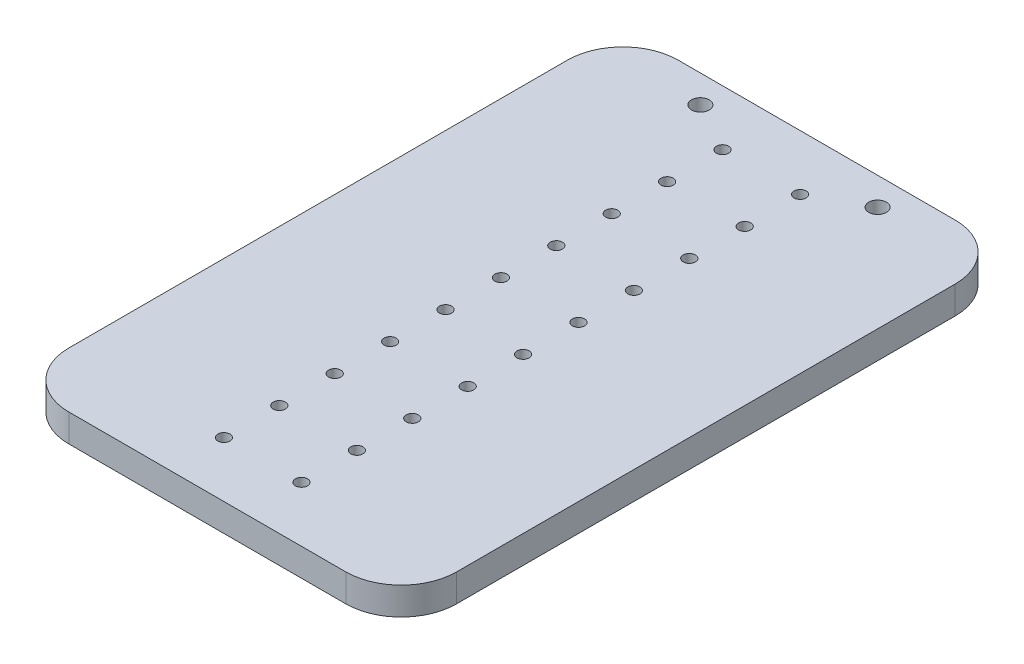
SolidWorks part; units mm, degrees
ref_plane "前视基准面" through (0, 0, 0) normal (0, 0, 1) x (1, 0, 0)
ref_plane "上视基准面" through (0, 0, 0) normal (0, 1, 0) x (1, 0, 0)
ref_plane "右视基准面" through (0, 0, 0) normal (1, 0, 0) x (0, 0, -1)
sketch "草图1" plane through (0, 0, 0) normal (0, 1, 0) x (1, 0, 0)
  line L0 (0, -113.2634) -> (0, 113.2634) construction
  line L1 (-35, 55) -> (35, 55)
  line L2 (-35, 55) -> (-35, -55)
  line L3 (-35, -55) -> (35, -55)
  line L4 (35, 55) -> (35, -55)
  line L5 (-35, 55) -> (35, -55) construction
  line L6 (-35, -55) -> (35, 55) construction
  circle A0 centre (-16, 50) radius 1.6
  circle A1 centre (-7, 35) radius 1.1
  circle A2 centre (-7, -45) radius 1.1
  circle A3 centre (7, -45) radius 1.1
  circle A4 centre (7, 35) radius 1.1
  circle A5 centre (16, 50) radius 1.6
  circle A6 centre (-7, 25) radius 1.1
  circle A7 centre (7, 25) radius 1.1
  circle A8 centre (-7, 15) radius 1.1
  circle A9 centre (7, 15) radius 1.1
  circle A10 centre (-7, 5) radius 1.1
  circle A11 centre (7, 5) radius 1.1
  circle A12 centre (-7, -5) radius 1.1
  circle A13 centre (7, -5) radius 1.1
  circle A14 centre (-7, -15) radius 1.1
  circle A15 centre (7, -15) radius 1.1
  circle A16 centre (-7, -25) radius 1.1
  circle A17 centre (7, -25) radius 1.1
  circle A18 centre (-7, -35) radius 1.1
  circle A19 centre (7, -35) radius 1.1
  circle A20 centre (-7, 45) radius 1.1
  circle A21 centre (7, 45) radius 1.1
  point P0 (0, 0)
  point P9 (0, 0)
  dimension "D4" = 3.2
  dimension "D6" = 2.2
  dimension "D8" = 2.2
  dimension "D1" = 70
  dimension "D2" = 110
  dimension "D3" = 5
  dimension "D5" = 16
  dimension "D7" = 7
  dimension "D9" = 80
  dimension "D10" = 10
  dimension "D11" = 8
  dimension "D12" = 2
extrude "凸台-拉伸1" add sketch "草图1" along normal blind 5
fillet "圆角1" radius 10 4 edges at (-35, 2.5, 55) (35, 2.5, 55) (35, 2.5, -55) (-35, 2.5, -55)
sketch "草图3" plane through (0, 0, 0) normal (0, 1, 0) x (1, 0, 0)
  line L0 (-17.3205, 10) -> (0, 0) construction
  line L1 (0, 0) -> (-17.3205, -10) construction
  line L2 (0, 0) -> (0, 10.0749) construction
  circle A0 centre (0, 0) radius 20 construction
  arc A1 (-17.3205, 10) -> (-17.3205, -10) centre (0, 0) ccw construction
  arc A2 (-20.3516, 11.75) -> (-20.3516, -11.75) centre (0, 0) ccw
  arc A3 (-14.2894, 8.25) -> (-14.2894, -8.25) centre (0, 0) ccw
  arc A4 (-14.2894, 8.25) -> (-20.3516, 11.75) centre (-17.3205, 10) ccw
  arc A5 (-20.3516, -11.75) -> (-14.2894, -8.25) centre (-17.3205, -10) ccw
  arc A6 (10, 17.3205) -> (-10, 17.3205) centre (0, 0) ccw construction
  arc A7 (11.75, 20.3516) -> (-11.75, 20.3516) centre (0, 0) ccw
  arc A8 (8.25, 14.2894) -> (-8.25, 14.2894) centre (0, 0) ccw
  arc A9 (8.25, 14.2894) -> (11.75, 20.3516) centre (10, 17.3205) ccw
  arc A10 (-11.75, 20.3516) -> (-8.25, 14.2894) centre (-10, 17.3205) ccw
  arc A11 (17.3205, -10) -> (17.3205, 10) centre (0, 0) ccw construction
  arc A12 (20.3516, -11.75) -> (20.3516, 11.75) centre (0, 0) ccw
  arc A13 (14.2894, -8.25) -> (14.2894, 8.25) centre (0, 0) ccw
  arc A14 (14.2894, -8.25) -> (20.3516, -11.75) centre (17.3205, -10) ccw
  arc A15 (20.3516, 11.75) -> (14.2894, 8.25) centre (17.3205, 10) ccw
  arc A16 (-10, -17.3205) -> (10, -17.3205) centre (0, 0) ccw construction
  arc A17 (-11.75, -20.3516) -> (11.75, -20.3516) centre (0, 0) ccw
  arc A18 (-8.25, -14.2894) -> (8.25, -14.2894) centre (0, 0) ccw
  arc A19 (-8.25, -14.2894) -> (-11.75, -20.3516) centre (-10, -17.3205) ccw
  arc A20 (11.75, -20.3516) -> (8.25, -14.2894) centre (10, -17.3205) ccw
  circle A21 centre (0, 0) radius 4
  point P5 (-20, 0)
  point P19 (0, 20)
  point P26 (20, 0)
  point P33 (0, -20)
  point P38 (0, 0)
  dimension "D1" = 60
  dimension "D3" = 3.5
  dimension "D5" = 8
  dimension "D2" = 60
  dimension "D4" = 4
extrude "切除-拉伸2" [suppressed] cut sketch "草图3" along normal blind 5
